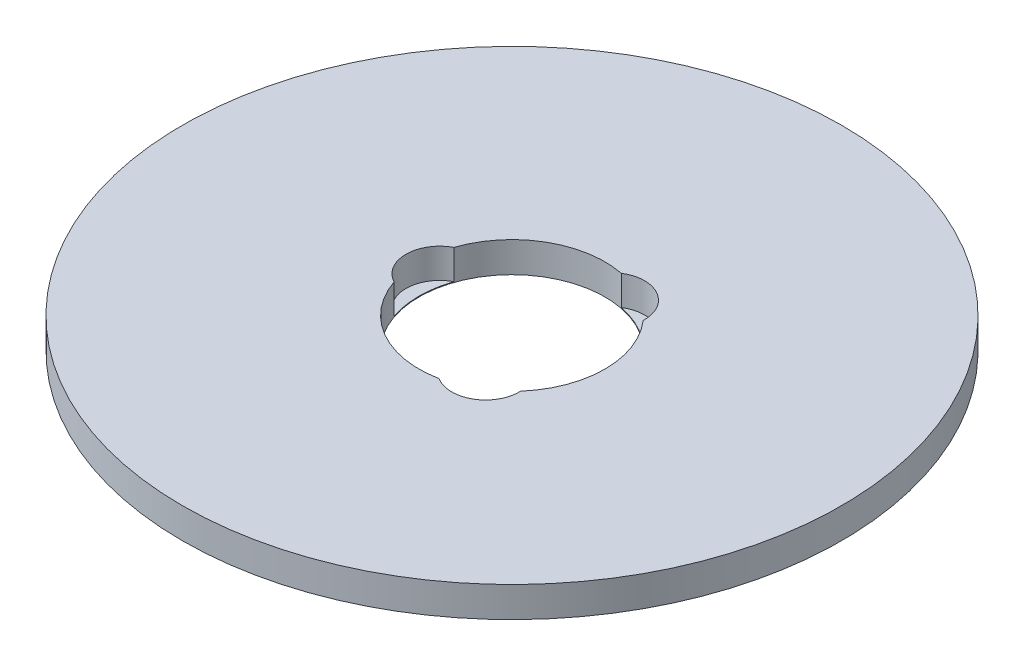
SolidWorks part; units mm, degrees
ref_plane "Front Plane" through (0, 0, 0) normal (0, 0, 1) x (1, 0, 0)
ref_plane "Top Plane" through (0, 0, 0) normal (0, 1, 0) x (1, 0, 0)
ref_plane "Right Plane" through (0, 0, 0) normal (1, 0, 0) x (0, 0, -1)
sketch "Sketch1" plane through (0, 0, 0) normal (0, 1, 0) x (1, 0, 0)
  circle A0 centre (0, 0) radius 97.5
  dimension "FLANGE_OD" = 195
extrude "Boss-Extrude1" add sketch "Sketch1" along normal blind 9
sketch "Sketch2" plane through (0, 0, 0) normal (0, 1, 0) x (1, 0, 0)
  circle A0 centre (0, 0) radius 27.5
  dimension "BORE_D" = 55
extrude "Cut-Extrude1" cut sketch "Sketch2" along normal through all
sketch "Sketch3" plane through (0, 9, 0) normal (0, 1, 0) x (1, 0, 0)
  circle A0 centre (0, 0) radius 21.3773 construction
  circle A1 centre (-21.3773, 0) radius 10
  dimension "BOLT_D" = 20
  dimension "BOLT_PCD" = 42.7547
extrude "Cut-Extrude2" cut sketch "Sketch3" against normal blind 8.7855
pattern_circular "CirPattern1" count 3 over 360 about axis through (0, 0, 0) along (0, 1, 0) of "Cut-Extrude2"
